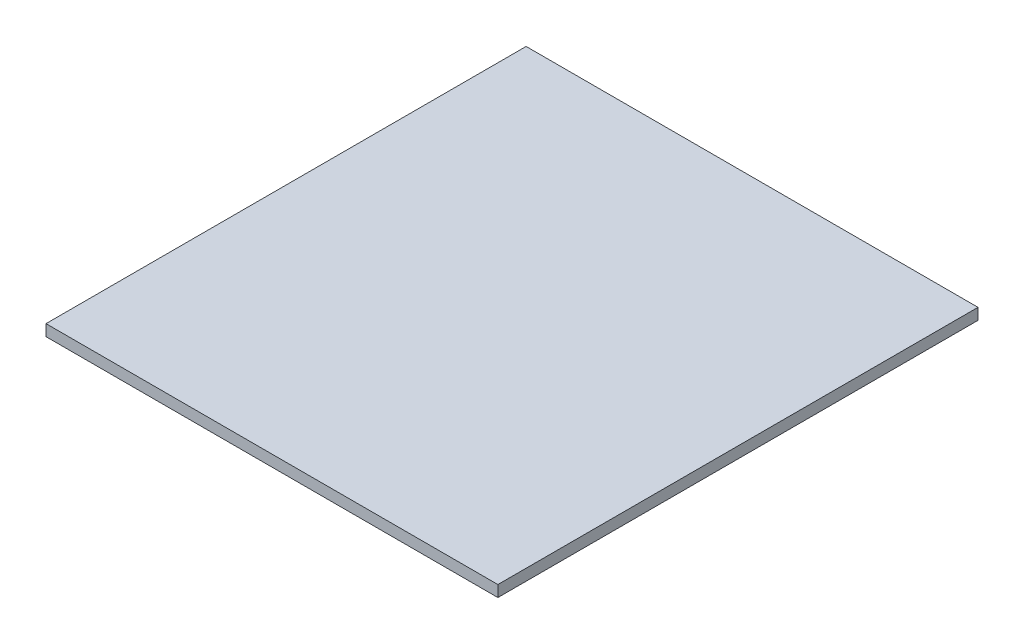
SolidWorks part; units mm, degrees
ref_plane "Спереди" through (0, 0, 0) normal (0, 0, 1) x (1, 0, 0)
ref_plane "Сверху" through (0, 0, 0) normal (0, 1, 0) x (1, 0, 0)
ref_plane "Справа" through (0, 0, 0) normal (1, 0, 0) x (0, 0, -1)
sketch "Эскиз1" plane through (0, 0, 0) normal (0, 1, 0) x (1, 0, 0)
  line L1 (-58.4225, 39.8335) -> (741.5775, 39.8335)
  line L2 (-58.4225, 39.8335) -> (-58.4225, -810.1665)
  line L3 (-58.4225, -810.1665) -> (741.5775, -810.1665)
  line L4 (741.5775, 39.8335) -> (741.5775, -810.1665)
  dimension "D1" = 800
  dimension "D2" = 850
sheet metal parameters "Листовой металл1" thickness 20 parameters "D1"=1.1, "Толщина"=20
base flange "Базовая кромка1" sketch "Эскиз1" thickness 20 reverse thickness direction no parameters "D1"=1.1
flat pattern "Развертка1" [suppressed]
sketch "Сгиб-Линии1" plane through (0, 0, 0) normal (0, 1, 0) x (1, 0, 0)
sketch3d "Граничная рамка1" [suppressed]
  line L0 (58.4225, 39.8335, 0) -> (58.4225, -1010.1665, 0) construction
  line L1 (-941.5775, 39.8335, 0) -> (-941.5775, -1010.1665, 0) construction
  line L2 (58.4225, 39.8335, 0) -> (-941.5775, 39.8335, 0) construction
  line L3 (58.4225, -1010.1665, 0) -> (-941.5775, -1010.1665, 0) construction
